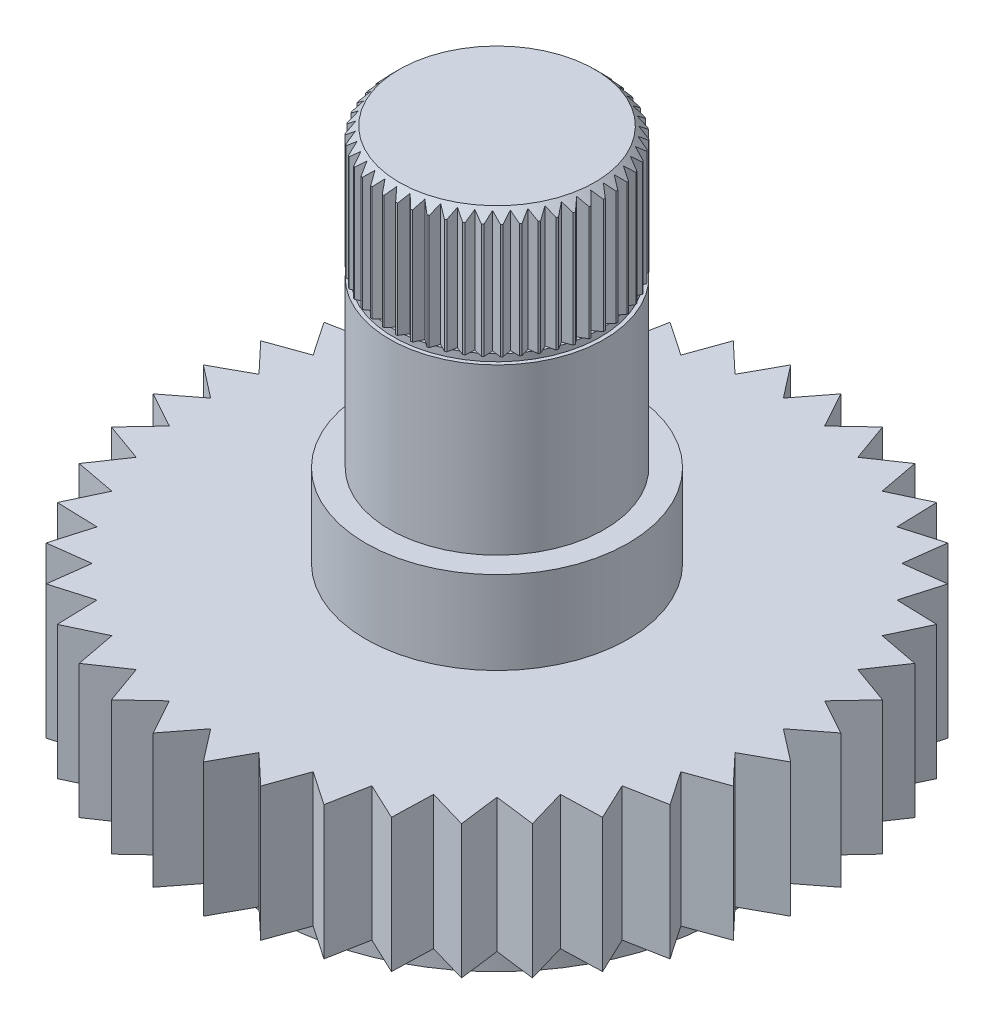
SolidWorks part; units mm, degrees
note: '?' marks a value the reader was unsure of.
material "Chrome Stainless Steel"
ref_plane "Front Plane" through (0, 0, 0) normal (0, 0, 1) x (1, 0, 0)
ref_plane "Top Plane" through (0, 0, 0) normal (0, 1, 0) x (1, 0, 0)
ref_plane "Right Plane" through (0, 0, 0) normal (1, 0, 0) x (0, 0, -1)
sketch "Sketch1" plane through (0, 0, 0) normal (0, 0, 1) x (1, 0, 0)
  line L0 (0, 0) -> (0, 35.5657) construction
  line L1 (6.016, 0) -> (8.509, 0)
  line L2 (8.509, 0) -> (8.509, 3.556)
  line L3 (8.509, 3.556) -> (3.4925, 3.556)
  line L4 (2.8575, 5.7658) -> (2.8575, 10.1501)
  line L5 (2.8575, 13.6398) -> (0, 13.6398)
  line L6 (0, 13.6398) -> (0, 0.9398)
  line L7 (0, 0.9398) -> (5, 0.9398)
  line L8 (5, 0.9398) -> (5, -1.6002)
  line L9 (2.8575, 10.3378) -> (2.7555, 10.3378)
  line L10 (2.7555, 10.3378) -> (2.7555, 10.1501)
  line L11 (2.7555, 10.1501) -> (2.8575, 10.1501)
  line L12 (2.8575, 10.3378) -> (2.8575, 13.6398)
  line L13 (2.8575, 5.7658) -> (3.4925, 5.7658)
  line L14 (3.4925, 5.7658) -> (3.4925, 3.556)
  line L15 (6.016, 0) -> (6.016, -1.6002)
  line L16 (6.016, -1.6002) -> (5, -1.6002)
  dimension "D1" = 5.715
  dimension "D2" = 10
  dimension "D3" = 17.018
  dimension "D4" = 3.556
  dimension "D5" = 15.24
  dimension "D6" = 2.54
  dimension "D7" = 7.366
  dimension "D8" = 6.985
  dimension "D9" = 1.6002
  dimension "D10" = 1.016
  dimension "D11" = 3.302
revolve "Revolve1" add sketch "Sketch1" angle 360 about L0
sketch "Sketch2" plane through (0, 0.9398, 0) normal (0, -1, 0) x (1, 0, 0)
  line L0 (0, 1.5875) -> (0, -1.5875)
  arc A0 (0, 1.5875) -> (0, -1.5875) centre (0, 0) cw
  dimension "D1" = 1.5875
extrude "Cut-Extrude1" cut sketch "Sketch2" against normal blind 2.032
sketch "Sketch3" plane through (0, 3.556, 0) normal (0, 1, 0) x (-1, 0, 0)
  line L0 (0.6676, -8.4828) -> (0, -7.62)
  line L1 (0, -7.62) -> (-0.6676, -8.4828)
  line L2 (-0.6676, -8.4828) -> (-1.192, -7.5262) construction
  line L3 (-1.192, -7.5262) -> (0, 0) construction
  line L4 (0, 0) -> (-0.6676, -8.4828) construction
  line L5 (0, -7.62) -> (0, 0) construction
  circle A0 centre (0, 0) radius 8.509 construction
  arc A1 (-0.6676, -8.4828) -> (0.6676, -8.4828) centre (0, 0) ccw
  circle A2 centre (0, 0) radius 7.62 construction
  dimension "D1" = 9
extrude "Cut-Extrude2" cut sketch "Sketch3" against normal through all
pattern_circular "CirPattern1" count 40 over 360 about axis through (0, 0, 0) along (0, 1, 0) of "Cut-Extrude2"
chamfer "Chamfer1" distance 0.254 angle 45 1 edges at (0, 13.6398, -2.8575)
sketch "Sketch4" plane through (0, 13.6398, 0) normal (0, 1, 0) x (-1, 0, 0)
  line L0 (0.1555, -2.8533) -> (0, -2.667)
  line L1 (0, -2.667) -> (-0.1555, -2.8533)
  line L2 (-0.1555, -2.8533) -> (-0.2898, -2.6512) construction
  line L3 (-0.2898, -2.6512) -> (0, 0) construction
  line L4 (0, 0) -> (-0.1555, -2.8533) construction
  line L5 (0, -2.667) -> (0, 0) construction
  circle A0 centre (0, 0) radius 2.8575 construction
  circle A1 centre (0, 0) radius 2.667 construction
  arc A2 (-0.1555, -2.8533) -> (0.1555, -2.8533) centre (0, 0) ccw
  dimension "D2" = 5.334
  dimension "D1" = 6.238
extrude "Cut-Extrude3" cut sketch "Sketch4" against normal up to surface (3.302 mm away) up to face at (0, 10.3378, -2.8575)
pattern_circular "CirPattern2" count 50 over 360 about axis through (0, 0, 0) along (0, 1, 0) of "Cut-Extrude3"
ref_axis "Axis1" through (0, -31.0516, 0) along (0, 1, 0)?
equation "\"D1@Sketch3\"=360/\"D1@CirPattern1\""
